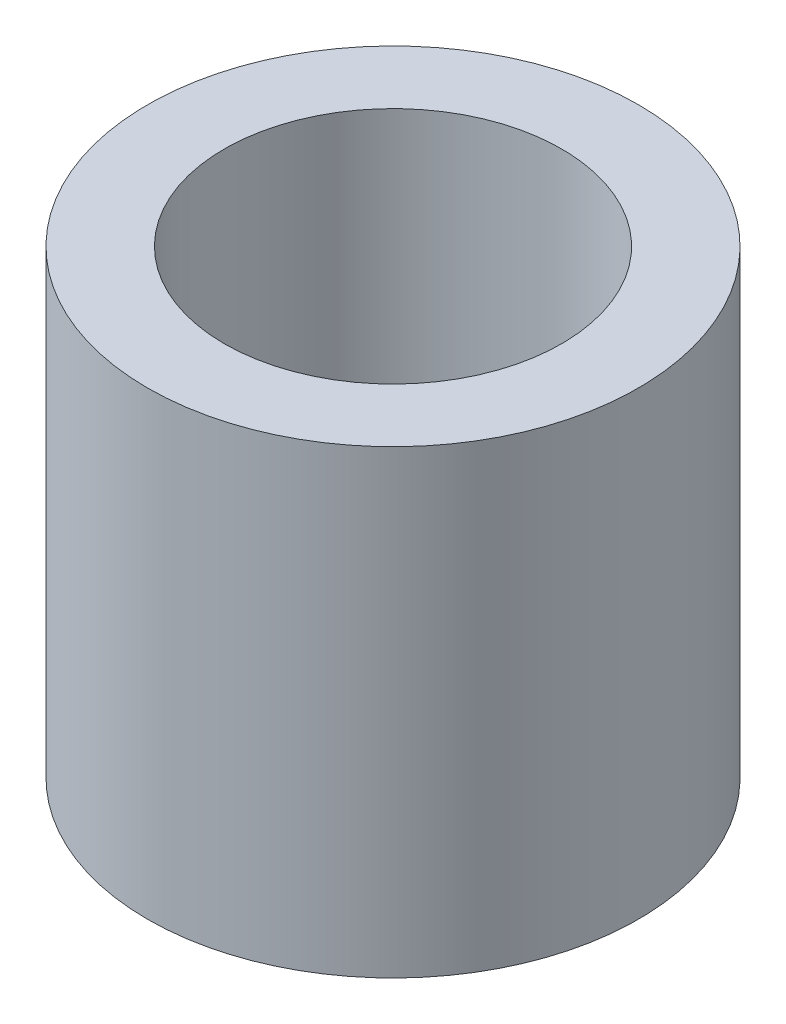
SolidWorks part; units mm, degrees
ref_plane "Front Plane" through (0, 0, 0) normal (0, 0, 1) x (1, 0, 0)
ref_plane "Top Plane" through (0, 0, 0) normal (0, 1, 0) x (1, 0, 0)
ref_plane "Right Plane" through (0, 0, 0) normal (1, 0, 0) x (0, 0, -1)
sketch "Sketch1" plane through (0, 0, 0) normal (0, 1, 0) x (1, 0, 0)
  circle A0 centre (0, 0) radius 2.75
  circle A1 centre (0, 0) radius 4
  circle A2 centre (0, 0) radius 1.25
  dimension "D1" = 5.5
  dimension "D2" = 8
  dimension "D3" = 2.5
extrude "Boss-Extrude1" add sketch "Sketch1" along normal blind 2 contours A0 A2 | A1 A0 region at (-2.6722, 0, 0) region at (-3.8869, 0, 0)
extrude "Boss-Extrude2" add sketch "Sketch1<3>" along normal offset from surface (7.5 mm away) 5.5 contours A1 A0 region at (-3.8869, 0, 0) up to face at (0, 2, 1.25) offset beyond the face yes
sketch "Sketch1<3>" plane through (0, 0, 0) normal (0, 1, 0) x (1, 0, 0) same geometry as "Sketch1"
